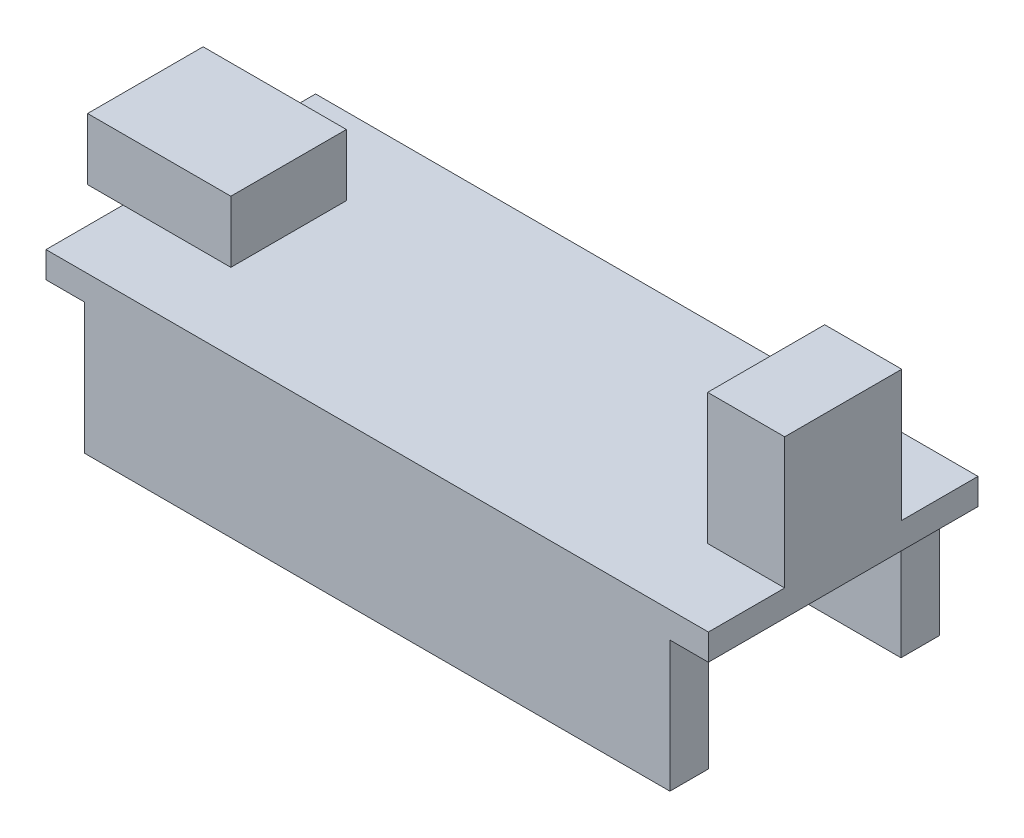
SolidWorks part; units mm, degrees
ref_plane "Front" through (0, 0, 0) normal (0, 0, 1) x (1, 0, 0)
ref_plane "Top" through (0, 0, 0) normal (0, 1, 0) x (1, 0, 0)
ref_plane "Right" through (0, 0, 0) normal (1, 0, 0) x (0, 0, -1)
sketch "Эскиз1" plane through (0, 0, 0) normal (0, 1, 0) x (1, 0, 0)
  line L1 (-21.5, 8.75) -> (21.5, 8.75)
  line L2 (-21.5, 8.75) -> (-21.5, -8.75)
  line L3 (-21.5, -8.75) -> (21.5, -8.75)
  line L4 (21.5, 8.75) -> (21.5, -8.75)
  line L5 (-21.5, 8.75) -> (21.5, -8.75) construction
  line L6 (-21.5, -8.75) -> (21.5, 8.75) construction
  point P0 (0, 0)
  dimension "D1" = 17.5
  dimension "D2" = 43
extrude "Бобышка-Вытянуть1" add sketch "Эскиз1" along normal blind 1.7
sketch "Эскиз2" plane through (0, 1.7, 0) normal (0, 1, 0) x (1, 0, 0)
  line L0 (21.5, -8.75) -> (21.5, 8.75) construction
  line L1 (21.5, 3.8) -> (16.5, 3.8)
  line L2 (21.5, 3.8) -> (21.5, -3.8)
  line L3 (21.5, -3.8) -> (16.5, -3.8)
  line L4 (16.5, 3.8) -> (16.5, -3.8)
  line L5 (-21.5, 0) -> (21.5, 0) construction
  line L7 (-21.5, 8.75) -> (-21.5, -8.75) construction
  line L9 (-14.5, 3.75) -> (-23.8, 3.75)
  line L10 (-14.5, 3.75) -> (-14.5, -3.75)
  line L11 (-14.5, -3.75) -> (-23.8, -3.75)
  line L12 (-23.8, 3.75) -> (-23.8, -3.75)
  point P11 (21.5, 0)
  point P16 (-14.5, 0)
  line M9 (21.5, -8.75) -> (21.5, 8.75)
  line M11 (-21.5, 8.75) -> (-21.5, -8.75)
  dimension "D1" = 5
  dimension "D2" = 7.6
  dimension "D3" = 7.5
  dimension "D4" = 9.3
  dimension "D5" = 7
extrude "Бобышка-Вытянуть2" add sketch "Эскиз2" along normal blind 8.5 contours L5 L4 L3 M9 | L4 L5 L2 L1 region at (19, 1.7, -1.9) region at (19, 1.7, 1.9)
extrude "Бобышка-Вытянуть3" add sketch "Эскиз2<3>" along normal blind 4 contours L5 L10 L9 M11 | L5 L11 L10 M11 | L9 L12 L11 M11 region at (-18, 1.7, 1.875) region at (-18, 1.7, -1.875) region at (-22.65, 1.7, 0)
sketch "Эскиз2<3>" plane through (0, 1.7, 0) normal (0, 1, 0) x (1, 0, 0) same geometry as "Эскиз2"
sketch "Эскиз4" plane through (0, 0, 0) normal (0, -1, 0) x (1, 0, 0)
  line L0 (-21.5, 0) -> (21.5, 0) construction
  line L1 (-21.5, -8.75) -> (-21.5, 8.75) construction
  line L2 (21.5, 8.75) -> (21.5, -8.75) construction
  line L3 (-21.5, 8.75) -> (21.5, 8.75) construction
  line L4 (-19, 8.75) -> (19, 8.75)
  line L5 (-19, 8.75) -> (-19, 6.25)
  line L6 (-19, 6.25) -> (19, 6.25)
  line L7 (19, 8.75) -> (19, 6.25)
  line L8 (21.5, -8.75) -> (-21.5, -8.75) construction
  line L9 (-19, -8.75) -> (19, -8.75)
  line L10 (-19, -8.75) -> (-19, -6.25)
  line L11 (-19, -6.25) -> (19, -6.25)
  line L12 (19, -8.75) -> (19, -6.25)
  dimension "D1" = 2.5
  dimension "D2" = 2.5
  dimension "D3" = 2.5
extrude "Бобышка-Вытянуть4" add sketch "Эскиз4" along normal blind 8.5
